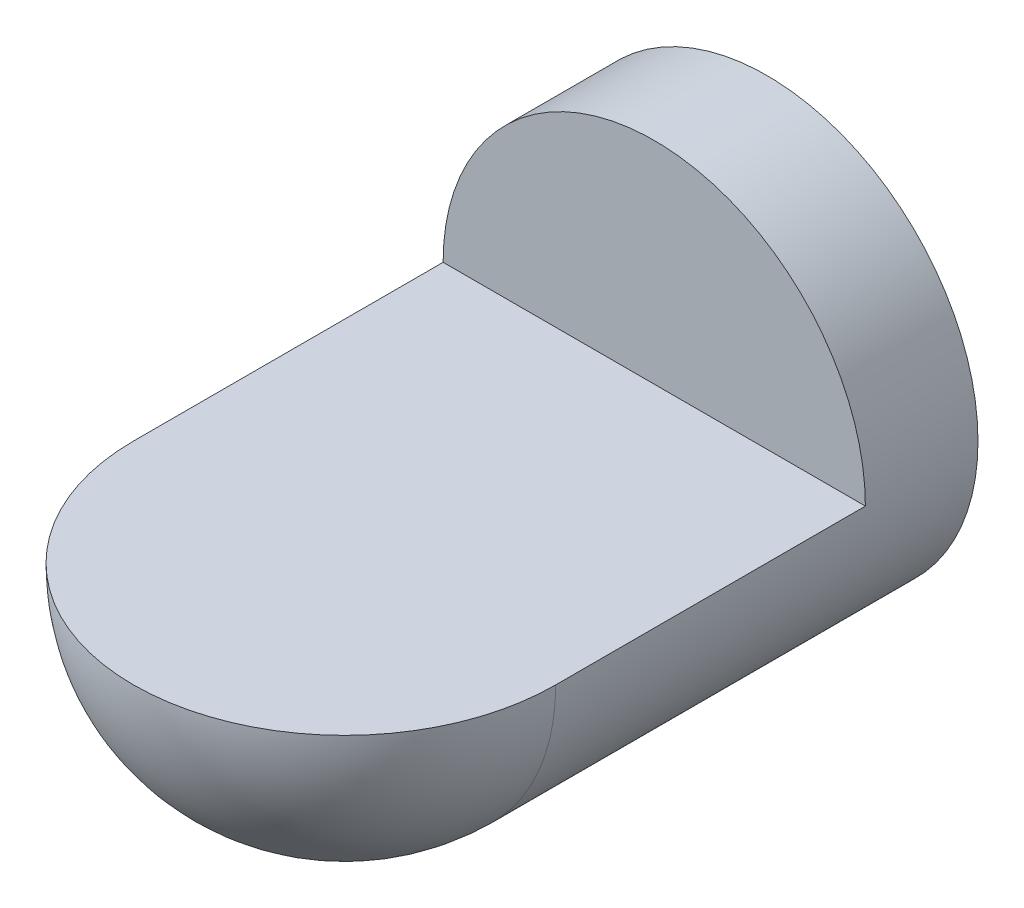
SolidWorks part; units mm, degrees
ref_plane "Front Plane" through (0, 0, 0) normal (0, 0, 1) x (1, 0, 0)
ref_plane "Top Plane" through (0, 0, 0) normal (0, 1, 0) x (1, 0, 0)
ref_plane "Right Plane" through (0, 0, 0) normal (1, 0, 0) x (0, 0, -1)
sketch "Sketch1" plane through (0, 0, 0) normal (1, 0, 0) x (0, 0, -1)
  line L0 (-146.9091, 0) -> (313.5945, 0) construction
  line L1 (150, 0) -> (-75, 0)
  line L2 (150, 0) -> (150, 75)
  line L3 (0, 75) -> (150, 75)
  arc A0 (-75, 0) -> (0, 75) centre (0, 0) cw
  dimension "D1" = 75
  dimension "D2" = 150
revolve "Revolve1" add sketch "Sketch1" angle 360 about L0
sketch "Sketch2" plane through (0, 0, 0) normal (1, 0, 0) x (0, 0, -1)
  line L0 (-88.0407, 0) -> (120.4455, 0) construction
  line L1 (110, 0) -> (110, 75)
  line L2 (150, 75) -> (0, 75) construction
  line L3 (110, 0) -> (-75, 0)
  line L4 (110, 75) -> (0, 75)
  line L5 (150, -75) -> (150, 75) construction
  arc A0 (0, 75) -> (0, -75) centre (0, 0) ccw construction
  arc A1 (-75, 0) -> (0, 75) centre (0, 0) cw
  dimension "D1" = 40
extrude "Cut-Extrude1" cut sketch "Sketch2" along normal through all and the other way through all
ref_axis "Axis1" through (0, 82.5, 0) along (0, -1, 0)
equation "\"link3_diameter\"=150"
equation "\"D1@Sketch1\"=\"link3_diameter\"/2"
equation "\"link3_length\"=150"
equation "\"D2@Sketch1\"=\"link3_length\""
equation "\"base_link_length\"=150"
equation "\"link1_diameter\"=150"
equation "\"link1_length\"=150"
equation "\"link2_diameter\"=150"
equation "\"link2_length\"=300"
equation "\"link4_diameter\"=150"
equation "\"link4_length\"=150"
equation "\"link5_diameter\"=150"
equation "\"link5_length\"=200"
equation "\"end_effector_diameter\"=150"
equation "\"end_effector_length\"=150"
equation "\"base_link_diameterA\"=200"
equation "\"base_link_diameterB\"=150"
equation "\"base_link_lengthA\"=50"
